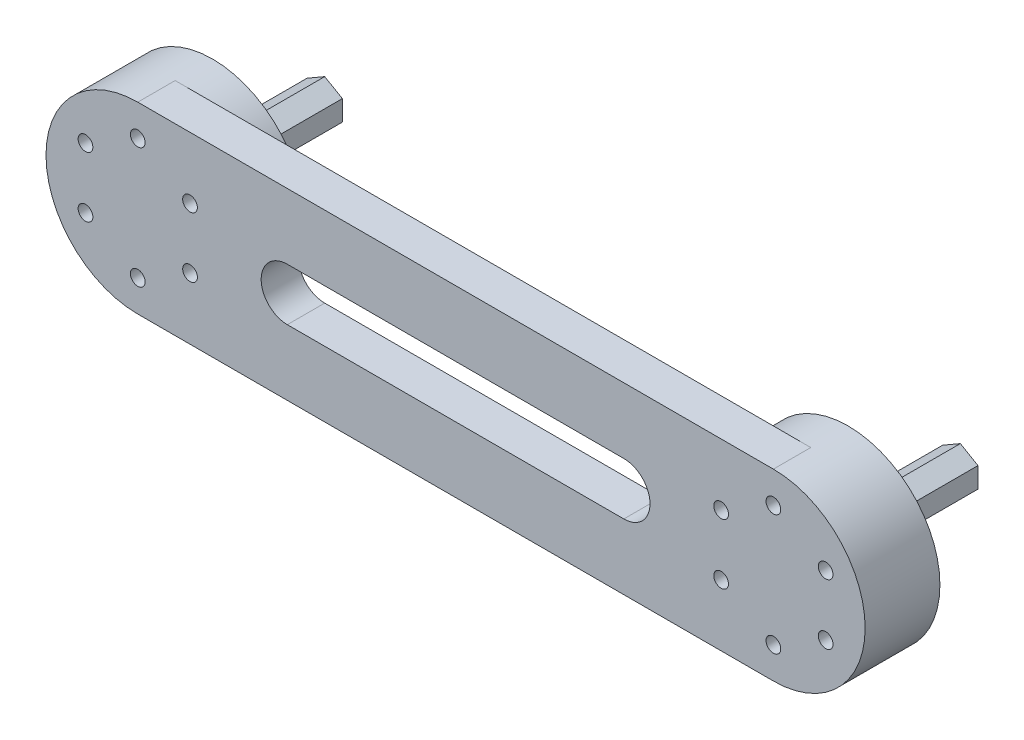
SolidWorks part; units mm, degrees
material "Cast Stainless Steel"
ref_plane "Front Plane" through (0, 0, 0) normal (0, 0, 1) x (1, 0, 0)
ref_plane "Top Plane" through (0, 0, 0) normal (0, 1, 0) x (1, 0, 0)
ref_plane "Right Plane" through (0, 0, 0) normal (1, 0, 0) x (0, 0, -1)
sketch "Sketch1" plane through (0, 0, 0) normal (0, 0, 1) x (1, 0, 0)
  line L0 (-86.7168, 15.1697) -> (-83.7168, 13.4376)
  line L1 (-83.7168, 13.4376) -> (-83.7168, 9.9735)
  line L2 (-83.7168, 9.9735) -> (-86.7168, 8.2415)
  line L3 (-86.7168, 8.2415) -> (-89.7168, 9.9735)
  line L4 (-89.7168, 9.9735) -> (-89.7168, 13.4376)
  line L5 (-89.7168, 13.4376) -> (-86.7168, 15.1697)
  line L6 (-86.7168, 27.2903) -> (21.2332, 27.2903)
  line L7 (-86.7168, -3.8792) -> (21.2332, -3.8792)
  line L9 (-61.3168, 16.1506) -> (-4.1668, 16.1506)
  line L10 (-61.3168, 7.2606) -> (-4.1668, 7.2606)
  line L11 (-32.7418, 16.1506) -> (-32.7418, 27.2903) construction
  line L12 (-32.7418, 7.2606) -> (-32.7418, -3.8792) construction
  line L13 (24.2332, 13.4376) -> (21.2332, 15.1697)
  line L14 (24.2332, 9.9735) -> (24.2332, 13.4376)
  line L15 (21.2332, 8.2415) -> (24.2332, 9.9735)
  line L16 (18.2332, 9.9735) -> (21.2332, 8.2415)
  line L17 (18.2332, 13.4376) -> (18.2332, 9.9735)
  line L18 (21.2332, 15.1697) -> (18.2332, 13.4376)
  circle A7 centre (-86.7168, 11.7056) radius 15.5847
  circle A8 centre (-86.7168, 21.9556) radius 1.25
  circle A9 centre (-95.5935, 16.8306) radius 1.25
  circle A10 centre (-95.5935, 6.5806) radius 1.25
  circle A11 centre (-86.7168, 1.4556) radius 1.25
  circle A12 centre (-77.84, 6.5806) radius 1.25
  circle A13 centre (-77.84, 16.8306) radius 1.25
  arc A14 (-86.7168, 27.2903) -> (-86.7168, -3.8792) centre (-86.7168, 11.7056) cw
  arc A16 (-61.3168, 16.1506) -> (-61.3168, 7.2606) centre (-61.3168, 11.7056) ccw
  arc A18 (-4.1668, 16.1506) -> (-4.1668, 7.2606) centre (-4.1668, 11.7056) cw
  arc A19 (21.2332, 27.2903) -> (21.2332, -3.8792) centre (21.2332, 11.7056) ccw
  circle A20 centre (12.3565, 16.8306) radius 1.25
  circle A21 centre (12.3565, 6.5806) radius 1.25
  circle A22 centre (21.2332, 1.4556) radius 1.25
  circle A23 centre (30.11, 6.5806) radius 1.25
  circle A24 centre (30.11, 16.8306) radius 1.25
  circle A25 centre (21.2332, 21.9556) radius 1.25
  circle A26 centre (21.2332, 11.7056) radius 15.5847
  point P9 (-32.7418, 7.2606)
  point P10 (-32.7418, 16.1506)
  point P19 (-32.7418, 11.7056)
  dimension "D5" = 4.445
  dimension "D6" = 12.3565
  dimension "D7" = 18.2332
  dimension "D16" = 31.1694
  dimension "D17" = 2.5
  dimension "D27" = 2.5
  dimension "D28" = 2.5
  dimension "D29" = 2.5
  dimension "D30" = 2.5
  dimension "D44" = 2.5
  dimension "D8" = 1.4556
  dimension "D9" = 28.575
  dimension "D10" = 25.4
  dimension "D15" = 10.25
  dimension "D18" = 83.7168
  dimension "D19" = 86.7168
  dimension "D20" = 3.4641
  dimension "D21" = 8.8768
  dimension "D22" = 8.2415
  dimension "D31" = 10.25
  dimension "D32" = 10.25
  dimension "D33" = 10.25
  dimension "D34" = 5.125
  dimension "D35" = 10.25
  dimension "D36" = 8.8768
  dimension "D37" = 10.25
  dimension "D39" = 8.8768
  dimension "D40" = 8.8768
  dimension "D41" = 25.4
extrude "Boss-Extrude5" add sketch "Sketch1" along normal blind 6.35 contours A19 L6 A7 L7 L9 A18 L10 A16 | A7 A13 A12 A11 A10 A9 A8 L4 L5 L0 L1 L2 L3 | A26 A19 A24 A22 A20 L18 L13 L14 L15 L16 L17 A21 A23 A25 region at (-32.7418, 26.1667, 0) region at (-76.0084, 22.4139, 0) region at (31.9416, 22.4139, 0)
extrude "Boss-Extrude6" add sketch "Sketch1<7>" against normal blind 6.35 contours A7 A13 A12 A11 A10 A9 A8 L4 L5 L0 L1 L2 L3 | A26 A19 A24 A22 A20 L18 L13 L14 L15 L16 L17 A21 A23 A25 region at (-76.0084, 22.4139, 0) region at (31.9416, 22.4139, 0)
sketch "Sketch1<7>" plane through (0, 0, 0) normal (0, 0, 1) x (1, 0, 0) same geometry as "Sketch1"
extrude "Boss-Extrude7" add sketch "Sketch1<8>" along normal blind 6.35 and the other way blind 25.4 contours L2 L3 L4 L5 L0 L1 | L15 L14 L13 L18 L17 L16
sketch "Sketch1<8>" plane through (0, 0, 0) normal (0, 0, 1) x (1, 0, 0) same geometry as "Sketch1"
